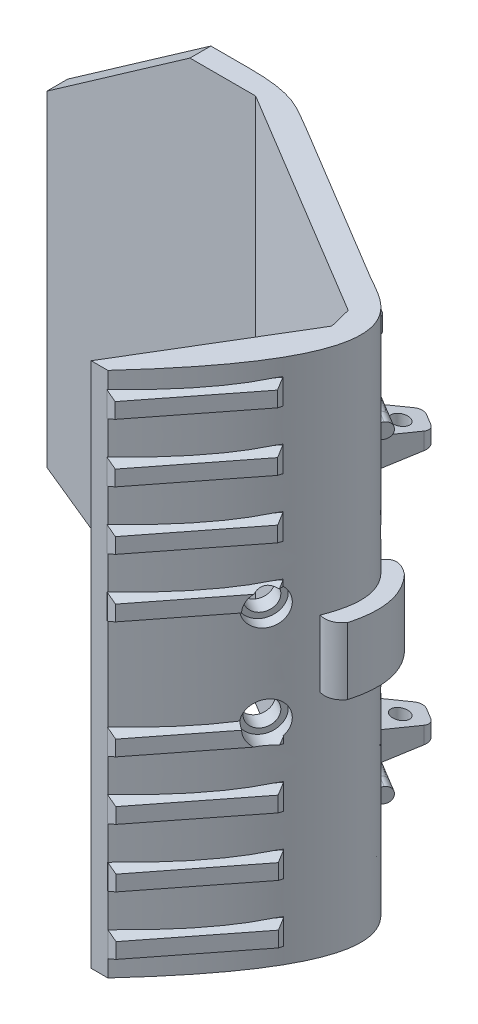
SolidWorks part; units mm, degrees
ref_plane "前视基准面" through (0, 0, 0) normal (0, 0, 1) x (1, 0, 0)
ref_plane "上视基准面" through (0, 0, 0) normal (0, 1, 0) x (1, 0, 0)
ref_plane "右视基准面" through (0, 0, 0) normal (1, 0, 0) x (0, 0, -1)
sketch "草图1" plane through (0, 0, 0) normal (0, 1, 0) x (1, 0, 0)
  line L5 (43.7362, -7.8141) -> (32.9204, -25.8147)
  line L6 (32.9204, -25.8147) -> (34.9204, -25.8147)
  line L7 (43.0861, -5.207) -> (15.3139, 11.4803)
  line L8 (12.0784, 13.9803) -> (10.0784, 13.9803)
  line L9 (40.9632, -0.4315) -> (21.9611, 10.9861)
  line L10 (10.0784, 13.9803) -> (-9.6861, 13.9803)
  line L11 (-9.6861, 11.4803) -> (15.3139, 11.4803)
  line L12 (-9.6861, 13.9803) -> (-9.6861, 11.4803)
  line L13 (43.7362, -7.8141) -> (43.0861, -5.207)
  line L14 (85.0447, -26.9183) -> (-3.1183, 26.0554) construction
  spline S0 degree 3 poles (12.0784, 13.9803) (18.0822, 13.9803) (19.1386, 12.5006) (21.9611, 10.9861) knots 0 0 0 0 0.428174 0.428174 0.428174 0.428174
  spline S1 degree 3 poles (40.9632, -0.4315) (44.691, -2.6714) (53.6124, -5.4172) (34.9204, -25.8147) knots 0.746299 0.746299 0.746299 0.746299 1 1 1 1
  point P3 (44.7148, -6.1855)
  dimension "D3" = 90
  dimension "D2" = 149
  dimension "D6" = 21
  dimension "D7" = 180
  dimension "D11" = 83
  dimension "D1" = 2
  dimension "D4" = 2
  dimension "D5" = 34.3
  dimension "D8" = 2.5
  dimension "D9" = 25
  dimension "D10" = 3
extrude "凸台-拉伸1" add sketch "草图1" along normal blind 63
sketch "草图2" plane through (10.6756, 0, -17.7672) normal (0.515, 0, -0.8572) x (-0.8572, 0, -0.515)
  line L0 (-13.1661, 31.5) -> (-35.3345, 31.5) construction
  line L1 (-13.1661, 63) -> (-13.1661, 0) construction
  line L2 (-35.3345, 63) -> (-35.3345, 0) construction
  line L4 (-32.3345, 24.5) -> (-18.3345, 24.5)
  line L5 (-32.3345, 24.5) -> (-32.3345, 38.5)
  line L6 (-32.3345, 38.5) -> (-18.3345, 38.5)
  line L7 (-18.3345, 24.5) -> (-18.3345, 38.5)
  line L8 (-32.3345, 24.5) -> (-18.3345, 38.5) construction
  line L9 (-32.3345, 38.5) -> (-18.3345, 24.5) construction
  point P6 (-25.3345, 31.5)
  dimension "D1" = 14
  dimension "D2" = 14
  dimension "D3" = 3
extrude "凸台-拉伸2" add sketch "草图2" along normal blind 1 draft 25
sketch "草图6" plane through (0, 0, 0) normal (0, -1, 0) x (1, 0, 0)
  line L0 (13.0784, -13.9655) -> (24.6266, -11.9292)
  line L1 (15.3139, -11.4803) -> (43.0861, 5.207) construction
  spline S0 degree 3 poles (21.9611, -10.9861) (19.1386, -12.5006) (18.0822, -13.9803) (12.0784, -13.9803) knots 0 0 0 0 0.428174 0.428174 0.428174 0.428174 construction
  dimension "D1" = 21
  dimension "D2" = 1
ref_plane "基准面2" through (2.7826, 0, -15.7809) normal (0.1736, 0, -0.9848) x (0.9848, 0, 0.1736)
sketch "草图7" plane through (2.7826, 0, -15.7809) normal (0.1736, 0, -0.9848) x (0.9848, 0, 0.1736)
  line L1 (11.4673, -18.5) -> (22.4673, -18.5)
  line L2 (11.4673, -18.5) -> (11.4673, -44.5)
  line L3 (11.4673, -44.5) -> (22.4673, -44.5)
  line L4 (22.4673, -18.5) -> (22.4673, -44.5)
  line L5 (9.4673, -63) -> (9.4673, 0) construction
  line L7 (37.6151, -24.5) -> (24.5449, -24.5) construction
  line L8 (24.5449, -38.5) -> (37.6151, -38.5) construction
  dimension "D1" = 6
  dimension "D2" = 6
  dimension "D3" = 11
  dimension "D4" = 2
sketch "草图3" plane through (11.1906, 0, -18.6243) normal (0.515, 0, -0.8572) x (-0.8572, 0, -0.515)
  line L0 (-18.8008, 31.5) -> (-31.8682, 31.5) construction
  line L1 (-18.8008, 24.9663) -> (-18.8008, 38.0337) construction
  line L2 (-31.8682, 38.0337) -> (-31.8682, 24.9663) construction
  line L3 (-25.3345, 38.0337) -> (-25.3345, 24.9663) construction
  line L4 (-18.8008, 38.0337) -> (-31.8682, 38.0337) construction
  line L5 (-31.8682, 24.9663) -> (-18.8008, 24.9663) construction
  line L6 (-22.1526, 34.682) -> (-28.5165, 28.318) construction
  line L7 (-21.0919, 33.6213) -> (-27.4559, 27.2574)
  line L8 (-23.2132, 35.7426) -> (-29.5772, 29.3787)
  line L9 (-22.1526, 28.318) -> (-28.5165, 34.682) construction
  line L10 (-23.2132, 27.2574) -> (-29.5772, 33.6213)
  line L11 (-21.0919, 29.3787) -> (-27.4559, 35.7426)
  arc A0 (-21.0919, 33.6213) -> (-23.2132, 35.7426) centre (-22.1526, 34.682) ccw
  arc A1 (-29.5772, 29.3787) -> (-27.4559, 27.2574) centre (-28.5165, 28.318) ccw
  arc A2 (-23.2132, 27.2574) -> (-21.0919, 29.3787) centre (-22.1526, 28.318) ccw
  arc A3 (-27.4559, 35.7426) -> (-29.5772, 33.6213) centre (-28.5165, 34.682) ccw
  point P14 (-25.3345, 31.5)
  point P19 (-25.3345, 31.5)
  dimension "D1" = 3
  dimension "D2" = 3
  dimension "D3" = 9
  dimension "D4" = 9
extrude "切除-拉伸1" cut sketch "草图3" against normal blind 0.6 contours L7 A0 L8 L11 | L7 L11 L8 L10 | L10 A2 L11 L7 | L8 A1 L7 L10 | L11 A3 L10 L8 region at (30.7231, 34.0473, -6.8881) region at (30.7231, 28.9527, -6.8881) region at (32.9066, 31.5, -5.5761) region at (35.0901, 28.9527, -4.2641) region at (35.0901, 34.0473, -4.2641)
ref_plane "基准面1" through (10.1606, 0, -16.91) normal (-0.515, 0, 0.8572) x (0.8572, 0, 0.515)
extrude "凸台-拉伸4" add sketch "草图7" along normal blind 2 draft 35 and the other way blind 2
sketch "草图4" plane through (9.1305, 0, -15.1957) normal (-0.515, 0, 0.8572) x (0.8572, 0, 0.515)
  line L0 (41.5138, 31.5) -> (-14.9499, 31.5) construction
  line L1 (41.5138, 63) -> (41.5138, 0) construction
  line L2 (3.1528, 63) -> (3.1528, 0) construction
  circle A0 centre (9.6528, 25.5) radius 1.65
  circle A1 centre (9.6528, 37.5) radius 1.65
  dimension "D1" = 3.3
  dimension "D2" = 12
  dimension "D3" = 6.5
extrude "切除-拉伸2" cut sketch "草图4" against normal through all
sketch "草图5" plane through (10.1606, 0, -16.91) normal (-0.515, 0, 0.8572) x (0.8572, 0, 0.515)
  circle A0 centre (9.6528, 25.5) radius 2.3
  circle A1 centre (9.6528, 37.5) radius 2.3
  dimension "D1" = 4.6
extrude "切除-拉伸3" cut sketch "草图5" against normal through all
ref_plane "基准面3" through (2.7826, 0, -15.7809) normal (-0.1736, 0, 0.9848) x (0.9848, 0, 0.1736)
sketch "草图9" plane through (0, 0, 0) normal (0, -1, 0) x (1, 0, 0)
  line L0 (34.9204, 25.8147) -> (56.7509, -2.1272) construction
  line L4 (43.7362, 7.8141) -> (32.9204, 25.8147) construction
  dimension "D1" = 7
ref_plane "基准面4" through (34.2081, 0, 26.7263) normal (-0.788, 0, -0.6157) x (-0.6157, 0, 0.788)
sketch "草图10" plane through (34.2081, 0, 26.7263) normal (-0.788, 0, -0.6157) x (-0.6157, 0, 0.788)
  line L0 (-16.0854, 51) -> (-1.0854, 51)
  line L1 (-1.1569, 63) -> (-1.1569, 0) construction
  line L2 (-16.1569, 5) -> (-1.1569, 5)
  line L3 (-16.1569, 5) -> (-16.1569, 2)
  line L4 (-16.1569, 2) -> (-1.1569, 2)
  line L5 (-1.1569, 5) -> (-1.1569, 2)
  line L6 (-16.1467, 9) -> (-1.1467, 9)
  line L11 (-16.1467, 12) -> (-1.1467, 12)
  line L12 (-16.1467, 12) -> (-16.1467, 9)
  line L13 (-1.1467, 12) -> (-1.1467, 9)
  line L14 (-16.0854, 54) -> (-1.0854, 54)
  line L15 (-16.1365, 16) -> (-1.1365, 16)
  line L16 (-16.1365, 19) -> (-1.1365, 19)
  line L17 (-16.1365, 19) -> (-16.1365, 16)
  line L18 (-1.1365, 19) -> (-1.1365, 16)
  line L19 (-16.0854, 54) -> (-16.0854, 51)
  line L20 (-16.1263, 23) -> (-1.1263, 23)
  line L21 (-16.1263, 26) -> (-1.1263, 26)
  line L22 (-16.1263, 26) -> (-16.1263, 23)
  line L23 (-1.1263, 26) -> (-1.1263, 23)
  line L24 (-1.0854, 54) -> (-1.0854, 51)
  line L25 (-16.1161, 30) -> (-1.1161, 30)
  line L26 (-16.1161, 33) -> (-1.1161, 33)
  line L27 (-16.1161, 33) -> (-16.1161, 30)
  line L28 (-1.1161, 33) -> (-1.1161, 30)
  line L29 (-16.0752, 58) -> (-1.0752, 58)
  line L30 (-16.1058, 37) -> (-1.1058, 37)
  line L31 (-16.1058, 40) -> (-1.1058, 40)
  line L32 (-16.1058, 40) -> (-16.1058, 37)
  line L33 (-1.1058, 40) -> (-1.1058, 37)
  line L34 (-16.0752, 61) -> (-1.0752, 61)
  line L35 (-16.0956, 44) -> (-1.0956, 44)
  line L36 (-16.0956, 47) -> (-1.0956, 47)
  line L37 (-16.0956, 47) -> (-16.0956, 44)
  line L38 (-1.0956, 47) -> (-1.0956, 44)
  line L39 (-16.0752, 61) -> (-16.0752, 58)
  line L44 (-1.0752, 61) -> (-1.0752, 58)
  line L52 (-1.1569, 31.5) -> (-16.1161, 31.5) construction
  dimension "D1" = 3
  dimension "D2" = 9
  dimension "D3" = 15
extrude "凸台-拉伸6" add sketch "草图10" against normal blind 1 draft 30 and the other way blind 1 contours L5 L2 L3 L4 | L13 L11 L12 L6 | L23 L21 L22 L20 | L38 L36 L37 L35 | L16 L18 L15 L17 | L31 L33 L30 L32 | L0 L24 L14 L19 | L29 L44 L34 L39 region at (39.5378, 3.5, 19.9046) region at (39.5316, 10.5, 19.9126) region at (39.519, 24.5, 19.9287) region at (39.5001, 45.5, 19.9529)
sketch "草图12" plane through (35.5843, 0, 21.3812) normal (-0.8572, 0, -0.515) x (-0.515, 0, 0.8572)
  line L0 (5.1722, 31.5) -> (-9.4999, 31.5) construction
  line L1 (5.1722, 63) -> (5.1722, 0) construction
  line L2 (-17.7278, 63) -> (-17.7278, 0) construction
  circle A0 centre (-9.2278, 25.5) radius 1.65
  circle A1 centre (-9.2278, 37.5) radius 1.65
  dimension "D1" = 3.3
  dimension "D2" = 12
  dimension "D3" = 8.5
extrude "切除-拉伸4" cut sketch "草图12" against normal blind 2
sketch "草图13" plane through (37.2986, 0, 22.4113) normal (-0.8572, 0, -0.515) x (-0.515, 0, 0.8572)
  circle A0 centre (-9.2278, 25.5) radius 2.3
  circle A1 centre (-9.2278, 37.5) radius 2.3
  dimension "D1" = 4.6
extrude "切除-拉伸5" cut sketch "草图13" against normal through all
chamfer "倒角1" distance 12 angle 55 2 edges at (-9.6861, 63, -12.7303) (-9.6861, 0, -12.7303) first distance on face at (-9.6861, 31.5, -12.7303)
sketch "草图14" plane through (10.6756, 0, -17.7672) normal (0.515, 0, -0.8572) x (-0.8572, 0, -0.515)
  line L0 (-35.3345, 31.5) -> (5.0388, 31.5) construction
  line L1 (-35.3345, 63) -> (-35.3345, 0) construction
  line L2 (-35.3345, 63) -> (-13.1661, 63) construction
  line L3 (-28.1661, 54) -> (-18.1661, 54)
  line L4 (-28.1661, 54) -> (-28.1661, 59)
  line L5 (-28.1661, 59) -> (-18.1661, 59)
  line L6 (-18.1661, 54) -> (-18.1661, 59)
  line L7 (-13.1661, 63) -> (-13.1661, 44.5) construction
  line L8 (-28.1661, 9) -> (-28.1661, 4)
  line L9 (-28.1661, 4) -> (-18.1661, 4)
  line L10 (-18.1661, 9) -> (-18.1661, 4)
  line L11 (-28.1661, 9) -> (-18.1661, 9)
  dimension "D1" = 5
  dimension "D2" = 10
  dimension "D3" = 4
  dimension "D4" = 5
extrude "凸台-拉伸8" add sketch "草图14" along normal blind 1 draft 25
sketch "草图15" plane through (10.6756, 0, -17.7672) normal (0.515, 0, -0.8572) x (-0.8572, 0, -0.515)
  line L0 (-35.3345, 31.5) -> (9.9606, 31.5) construction
  line L1 (-21.1661, 45) -> (-16.1661, 45)
  line L2 (-21.1661, 45) -> (-21.1661, 48.5)
  line L3 (-21.1661, 48.5) -> (-16.1661, 48.5)
  line L4 (-16.1661, 45) -> (-16.1661, 48.5)
  line L5 (-35.3345, 63) -> (-35.3345, 0) construction
  line L6 (-13.1661, 63) -> (-13.1661, 44.5) construction
  line L7 (-27.1661, 63) -> (-27.1661, -8.1652) construction
  line L9 (-16.1661, 18) -> (-16.1661, 14.5)
  line L10 (-21.1661, 18) -> (-16.1661, 18)
  line L11 (-21.1661, 18) -> (-21.1661, 14.5)
  line L12 (-21.1661, 14.5) -> (-16.1661, 14.5)
  line L13 (-38.1661, 45) -> (-38.1661, 48.5)
  line L14 (-33.1661, 45) -> (-33.1661, 48.5)
  line L15 (-33.1661, 18) -> (-33.1661, 14.5)
  line L16 (-33.1661, 14.5) -> (-38.1661, 14.5)
  line L17 (-38.1661, 18) -> (-38.1661, 14.5)
  line L18 (-33.1661, 18) -> (-38.1661, 18)
  line L19 (-33.1661, 48.5) -> (-38.1661, 48.5)
  line L20 (-33.1661, 45) -> (-38.1661, 45)
  line L21 (-35.3345, 63) -> (-13.1661, 63) construction
  dimension "D1" = 5
  dimension "D2" = 3.5
  dimension "D3" = 3
  dimension "D4" = 14
  dimension "D5" = 14.5
extrude "凸台-拉伸9" add sketch "草图15" along normal blind 5 draft 10 and the other way blind 2
fillet "圆角1" radius 1 8 edges at (27.8635, 46.75, -13.2728) (30.6379, 46.75, -11.6058) (42.4354, 46.75, -4.5171) (45.2098, 46.75, -2.8501) (45.2098, 16.25, -2.8501) (42.4354, 16.25, -4.5171) (30.6379, 16.25, -11.6058) (27.8635, 16.25, -13.2728)
sketch "草图16" plane through (0, 0, 0) normal (0, 1, 0) x (1, 0, 0)
  line L0 (29.2507, 12.4393) -> (26.234, 6.8746) construction
  line L1 (28.5828, 12.8406) -> (29.9187, 12.0379) construction
  line L2 (43.8226, 3.6836) -> (40.6074, -2.1444) construction
  line L3 (43.1546, 4.085) -> (44.4905, 3.2823) construction
  circle A0 centre (28.0592, 10.2415) radius 1
  circle A1 centre (42.615, 1.4946) radius 1
  dimension "D1" = 2
  dimension "D2" = 2
  dimension "D3" = 2.5
  dimension "D4" = 2.5
extrude "切除-拉伸6" cut sketch "草图16" along normal through all
sketch "草图17" plane through (10.6756, 0, -17.7672) normal (0.515, 0, -0.8572) x (-0.8572, 0, -0.515)
  line L0 (-35.3345, 31.5) -> (6.1291, 31.5) construction
  line L1 (-27.1661, 13.5) -> (-40.1661, 13.5)
  line L2 (-27.1661, 13.5) -> (-27.1661, 11.7)
  line L3 (-27.1661, 11.7) -> (-40.1661, 11.7)
  line L4 (-40.1661, 13.5) -> (-40.1661, 11.7)
  line L5 (-35.3345, 45) -> (-35.3345, 18) construction
  line L6 (-40.1661, 49.5) -> (-40.1661, 51.3)
  line L7 (-27.1661, 49.5) -> (-40.1661, 49.5)
  line L8 (-27.1661, 49.5) -> (-27.1661, 51.3)
  line L9 (-27.1661, 51.3) -> (-40.1661, 51.3)
  line L10 (-33.1661, 14.5) -> (-33.1661, 18) construction
  dimension "D1" = 1.8
  dimension "D2" = 1
  dimension "D3" = 13
  dimension "D4" = 6
extrude "凸台-拉伸11" add sketch "草图17" along normal blind 0.9 and the other way blind 2
fillet "圆角2" radius 0.9 4 edges at (39.9966, 13.5, -1.1993) (39.9966, 11.7, -1.1993) (39.9966, 51.3, -1.1993) (39.9966, 49.5, -1.1993)
ref_plane "基准面5" through (0, 31.5, 0) normal (0, 1, 0) x (1, 0, 0)
sketch "草图18" plane through (0, 31.5, 0) normal (0, 1, 0) x (1, 0, 0)
  spline S1 degree 3 poles (-800.1632, -575.9287) (959.9053, 492.5506) (-894.7394, -446.4514) (945.0175, 426.9856) knots 0.199223 0.199223 0.199223 0.199223 1.737221 1.737221 1.737221 1.737221 only from (34.9204, -25.8147) to (40.9632, -0.4315) construction
  spline S2 degree 3 poles (-1622.7373, -1143.399) (-243.9329, -253.0026) (4.0866, -70.6466) (43.8783, -18.0738) (45.1021, -16.208) (46.9538, -12.8326) (47.5833, -11.322) (48.1481, -9.2395) (48.2725, -8.5758) (48.3978, -7.3019) (48.3983, -6.6915) (48.2794, -5.5293) (48.1595, -4.9777) (47.8162, -3.95) (47.5929, -3.4745) (47.0757, -2.6099) (46.7823, -2.2209) (46.1608, -1.5235) (45.8328, -1.2147) (44.838, -0.3851) (44.1607, 0.0415) (43.2426, 0.5773) (42.9526, 0.7382) (29.304, 8.3517) (84.7832, -19.7991) (2023.3591, -270.2921) knots -2.890155 -2.890155 -2.890155 -2.890155 0.125 0.125 0.25 0.25 0.375 0.375 0.4375 0.4375 0.5 0.5 0.5625 0.5625 0.625 0.625 0.6875 0.6875 0.75 0.75 0.875 0.875 0.9375 0.9375 4.11529 4.11529 4.11529 4.11529 only from (36.3949, -27.1659) to (41.9933, 1.2829)
  spline S3 degree 3 poles (47.9088, -10.1172) (47.9263, -10.0558) (47.9433, -9.9946) (48.1481, -9.2395) (48.2725, -8.5758) (48.3978, -7.3019) (48.3983, -6.6915) (48.2794, -5.5293) (48.1595, -4.9777) (47.8162, -3.95) (47.5929, -3.4745) (47.0757, -2.6099) (46.7823, -2.2209) (46.4253, -1.8203) (46.3786, -1.7693) (46.3316, -1.7191) knots 0.369513 0.369513 0.369513 0.369513 0.375 0.375 0.4375 0.4375 0.5 0.5 0.5625 0.5625 0.625 0.625 0.6875 0.6875 0.696808 0.696808 0.696808 0.696808
  spline S4 degree 3 poles (45.4987, -10.9892) (47.6291, -5.6106) (45.5233, -3.2478) (43.2588, -1.77) knots 0.828302 0.828302 0.828302 0.828302 0.95491 0.95491 0.95491 0.95491
  spline S5 degree 2 poles (47.9088, -10.1172) (46.9495, -11.3683) (45.4987, -10.9892) knots 0 0 0 1 1 1
  spline S6 degree 3 poles (46.3316, -1.7191) (44.5574, -0.278) (43.7585, -0.9443) (43.2588, -1.77) knots 0 0 0 0 1 1 1 1
  dimension "D1" = 2
extrude "凸台-拉伸12" add sketch "草图18" along normal blind 4 and the other way blind 4
sketch "草图19" plane through (0, 0, -13.9803) normal (0, 0, -1) x (-1, 0, 0)
  line L0 (-12.0784, 31.5) -> (21.1094, 31.5) construction
  line L1 (-12.0784, 63) -> (-12.0784, 0) construction
  line L2 (-17.4387, 54.5) -> (-17.4387, 50.5)
  line L3 (-17.4387, 8.5) -> (-5.4387, 8.5)
  line L4 (-17.4387, 8.5) -> (-17.4387, 12.5)
  line L5 (-17.4387, 12.5) -> (-5.4387, 12.5)
  line L6 (-5.4387, 8.5) -> (-5.4387, 12.5)
  line L7 (-17.4387, 54.5) -> (-5.4387, 54.5)
  line L8 (-5.4387, 54.5) -> (-5.4387, 50.5)
  line L9 (-17.4387, 50.5) -> (-5.4387, 50.5)
  dimension "D1" = 4
  dimension "D2" = 12
  dimension "D3" = 19
extrude "凸台-拉伸13" add sketch "草图19" along normal blind 1.5 draft 10 and the other way blind 2 draft 10
equation "\"M3_1\"= 3.3"
equation "\"D1@草图12\"=\"M3_1\""
equation "\"D1@草图4\"=\"M3_1\""
